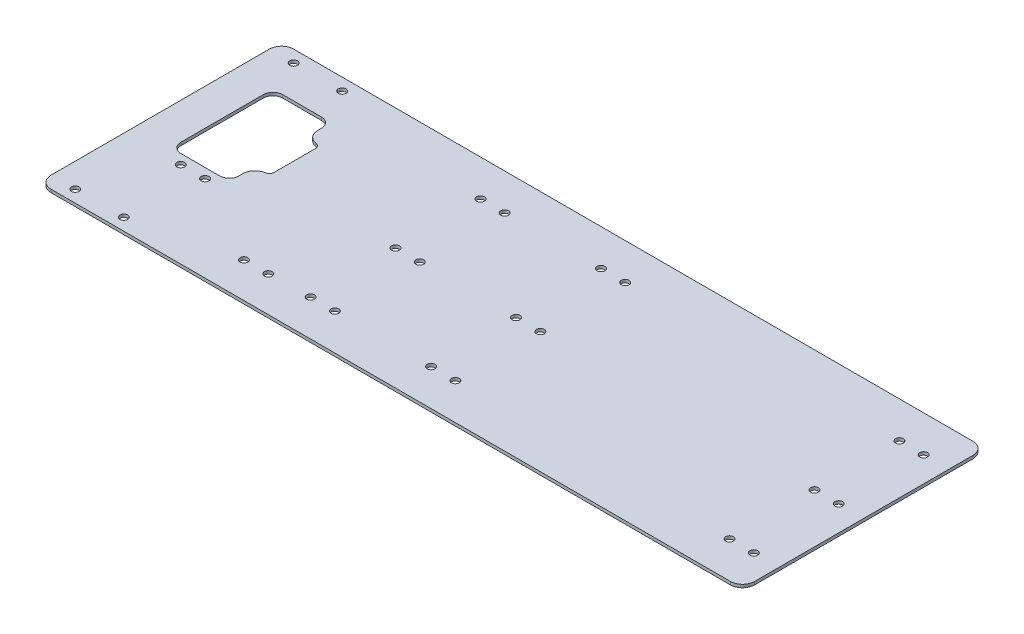
SolidWorks part; units mm, degrees
ref_plane "Front Plane" through (0, 0, 0) normal (0, 0, 1) x (1, 0, 0)
ref_plane "Top Plane" through (0, 0, 0) normal (0, 1, 0) x (1, 0, 0)
ref_plane "Right Plane" through (0, 0, 0) normal (1, 0, 0) x (0, 0, -1)
sketch "Sketch1" plane through (0, 0, 0) normal (0, 1, 0) x (1, 0, 0)
  line L0 (171.0189, 63.5) -> (171.0189, 44.45) construction
  line L1 (184.15, 63.5) -> (-184.15, 63.5)
  line L2 (184.15, 63.5) -> (184.15, -63.5)
  line L3 (184.15, -63.5) -> (-184.15, -63.5)
  line L4 (-184.15, 63.5) -> (-184.15, -63.5)
  line L5 (184.15, 63.5) -> (-184.15, -63.5) construction
  line L6 (184.15, -63.5) -> (-184.15, 63.5) construction
  line L7 (-128.2684, -0.635) -> (-128.2684, 31.115) construction
  line L8 (-128.2684, 31.115) -> (-134.6184, 31.115) construction
  line L9 (-128.2684, 5.715) -> (-134.6184, 5.715) construction
  line L12 (-165.0984, -13.335) -> (-165.0984, 40.005)
  line L15 (-134.6184, -13.335) -> (-165.0984, -13.335)
  line L17 (-134.6184, 40.005) -> (-165.0984, 40.005)
  line L18 (0, 63.5) -> (0, -63.5) construction
  line L19 (-134.6184, 40.005) -> (-134.6184, -13.335)
  line L20 (171.0189, 44.45) -> (184.15, 44.45) construction
  line L21 (0, 0) -> (-126.9984, 0) construction
  line L22 (-82.55, -45.0215) -> (-95.25, -45.0215) construction
  line L23 (171.0189, 44.45) -> (171.0189, 0) construction
  line L25 (171.0189, 0) -> (171.0189, -44.45) construction
  line L26 (171.0189, 44.45) -> (158.3189, 44.45) construction
  line L30 (171.0189, 0) -> (158.3189, 0) construction
  line L31 (171.0189, -44.45) -> (158.3189, -44.45) construction
  line L32 (158.3189, 44.45) -> (14.8089, 44.45) construction
  line L33 (14.8089, 44.45) -> (14.8089, 0) construction
  line L34 (14.8089, 0) -> (14.8089, -44.45) construction
  line L35 (-146.05, -57.15) -> (-184.15, -57.15) construction
  line L36 (-146.05, 57.15) -> (-184.15, 57.15) construction
  line L37 (-128.2684, -0.635) -> (-128.2684, 5.715) construction
  line L38 (-184.15, -18.415) -> (-154.94, -18.415) construction
  line L39 (-154.94, -18.415) -> (-142.24, -18.415) construction
  line L40 (-134.6184, 26.67) -> (-126.9984, 26.67)
  line L41 (-126.9984, 26.67) -> (-126.9984, 0)
  line L42 (-126.9984, 0) -> (-134.6184, 0)
  line L43 (14.8089, 44.45) -> (2.1089, 44.45) construction
  line L44 (14.8089, 0) -> (2.1089, 0) construction
  line L45 (14.8089, -44.45) -> (2.1089, -44.45) construction
  line L46 (2.1089, 44.45) -> (-48.2678, 44.45) construction
  line L47 (-48.2678, 44.45) -> (-60.9678, 44.45) construction
  line L48 (-48.2678, 44.45) -> (-48.2678, 0) construction
  line L49 (-48.2678, 0) -> (-60.9678, 0) construction
  line L50 (-48.2678, 0) -> (-48.2678, -44.45) construction
  line L51 (-48.2678, -44.45) -> (-60.9678, -44.45) construction
  circle A12 centre (-146.05, -57.15) radius 2.032
  circle A13 centre (-171.45, -57.15) radius 2.032
  circle A14 centre (-146.05, 57.15) radius 2.032
  circle A15 centre (-171.45, 57.15) radius 2.032
  circle A18 centre (-154.94, -18.415) radius 2.032
  circle A19 centre (-142.24, -18.415) radius 2.032
  circle A20 centre (-95.25, -45.0215) radius 2.032
  circle A21 centre (-82.55, -45.0215) radius 2.032
  circle A24 centre (171.0189, 44.45) radius 2.032
  circle A25 centre (171.0189, 0) radius 2.032
  circle A26 centre (171.0189, -44.45) radius 2.032
  circle A27 centre (158.3189, 44.45) radius 2.032
  circle A28 centre (158.3189, 0) radius 2.032
  circle A29 centre (158.3189, -44.45) radius 2.032
  circle A30 centre (2.1089, 44.45) radius 2.032
  circle A31 centre (2.1089, 0) radius 2.032
  circle A32 centre (2.1089, -44.45) radius 2.032
  circle A33 centre (14.8089, -44.45) radius 2.032
  circle A34 centre (14.8089, 0) radius 2.032
  circle A35 centre (14.8089, 44.45) radius 2.032
  circle A36 centre (-60.9678, 44.45) radius 2.032
  circle A37 centre (-48.2678, 44.45) radius 2.032
  circle A38 centre (-60.9678, 0) radius 2.032
  circle A39 centre (-60.9678, -44.45) radius 2.032
  circle A40 centre (-48.2678, -44.45) radius 2.032
  circle A41 centre (-48.2678, 0) radius 2.032
  point P0 (0, 0)
  point P11 (-128.2684, -0.635)
  point P13 (-134.6184, 31.115)
  point P17 (-134.6184, 5.715)
  point P37 (0, 0)
  dimension "D5" = 13.335
  dimension "D6" = 29.21
  dimension "D18" = 12.7
  dimension "D13" = 4.064
  dimension "D23" = 44.45
  dimension "D24" = 44.45
  dimension "D31" = 12.7
  dimension "D32" = 143.51
  dimension "D35" = 50.3767
  dimension "D1" = 368.3
  dimension "D2" = 127
  dimension "D3" = 128.27
  dimension "D4" = 25.4
  dimension "D7" = 6.35
  dimension "D8" = 30.48
  dimension "D9" = 53.34
  dimension "D10" = 8.89
  dimension "D11" = 19.05
  dimension "D12" = 12.7
  dimension "D14" = 38.1
  dimension "D15" = 6.35
  dimension "D16" = 12.7
  dimension "D17" = 6.35
  dimension "D19" = 31.75
  dimension "D20" = 19.05
  dimension "D21" = 13.1311
  dimension "D22" = 5.08
  dimension "D25" = 88.9
  dimension "D26" = 12.7
  dimension "D27" = 7.62
  dimension "D28" = 26.67
  dimension "D29" = 13.335
  dimension "D30" = 18.4785
  dimension "D33" = 44.45
  dimension "D34" = 44.45
extrude "Boss-Extrude1" add sketch "Sketch1" along normal blind 1.5875 contours L1 L4 L3 L2 A21 A20 A18 A14 A12 L41 L42 L19 L15 L12 L17 L40 A13 A15 A19 region at (6.1738, 0, 0.5099)
sketch "Sketch2" plane through (0, 1.5875, 0) normal (0, 1, 0) x (1, 0, 0)
  line L0 (-69.85, 63.5) -> (-69.85, -63.5)
  line L1 (184.15, 63.5) -> (-184.15, 63.5) construction
  line L2 (184.15, -63.5) -> (-184.15, -63.5) construction
  circle A0 centre (-82.55, -45.0215) radius 2.032 construction
  dimension "D1" = 12.7
extrude "Cut-Extrude1" [suppressed] cut sketch "Sketch2" against normal through all flip side to cut
fillet "Fillet1" radius 5.08 4 edges at (-134.6184, 0.7937, 13.335) (-165.0984, 0.7937, 13.335) (-165.0984, 0.7937, -40.005) (-134.6184, 0.7937, -40.005)
fillet "Fillet3" radius 6.35 4 edges at (184.15, 0.7937, 63.5) (184.15, 0.7937, -63.5) (-184.15, 0.7937, 63.5) (-184.15, 0.7937, -63.5)
fillet "Fillet4" radius 2.54 2 edges at (-126.9984, 0.7937, 0) (-126.9984, 0.7937, -26.67)
fillet "Fillet5" radius 6.35 2 edges at (-134.6184, 0.7937, 0) (-134.6184, 0.7937, -26.67)
fillet "Fillet6" [suppressed] radius 6.35
sketch "Sketch3" plane through (0, 1.5875, 0) normal (0, 1, 0) x (1, 0, 0)
  circle A0 centre (25.4, -25.4) radius 2.032
  circle A1 centre (25.4, 25.4) radius 2.032
  arc A2 (10.7648, -26.0196) -> (10.7648, -24.7804) centre (12.7, -25.4) ccw construction
  circle A3 centre (25.4, -25.4) radius 2.032 construction
  circle A4 centre (25.4, 25.4) radius 2.032 construction
  arc A5 (10.7648, 24.7804) -> (10.7648, 26.0196) centre (12.7, 25.4) ccw construction
  arc A6 (10.7648, 24.7804) -> (10.7648, 26.0196) centre (12.7, 25.4) ccw
  arc A7 (10.7648, -26.0196) -> (10.7648, -24.7804) centre (12.7, -25.4) ccw
  circle A9 centre (162.56, -44.45) radius 2.032 construction
  circle A10 centre (162.56, 44.45) radius 2.032 construction
  circle A12 centre (-2.54, -25.4) radius 2.032 construction
  circle A15 centre (-73.66, 44.45) radius 2.032 construction
  circle A16 centre (-73.66, -44.45) radius 2.032 construction
  circle A17 centre (25.4, -25.4) radius 2.032
  circle A18 centre (25.4, 25.4) radius 2.032
  circle A19 centre (-15.24, -25.4) radius 2.032 construction
  circle A20 centre (-15.24, 25.4) radius 2.032 construction
  circle A23 centre (162.56, -44.45) radius 2.032
  circle A24 centre (162.56, 44.45) radius 2.032
  circle A29 centre (12.7, -25.4) radius 2.032
  circle A31 centre (12.7, 25.4) radius 2.032
  circle A32 centre (175.26, 44.45) radius 2.032 construction
  circle A33 centre (175.26, -44.45) radius 2.032 construction
  circle A34 centre (175.26, 44.45) radius 2.032
  circle A35 centre (175.26, -44.45) radius 2.032
  circle A36 centre (-2.54, 25.4) radius 2.032 construction
  circle A41 centre (-2.54, -25.4) radius 2.032
  circle A42 centre (-2.54, 25.4) radius 2.032
  circle A54 centre (-73.66, 44.45) radius 2.032
  circle A55 centre (-73.66, -44.45) radius 2.032
  circle A56 centre (-15.24, -25.4) radius 2.032
  circle A57 centre (-15.24, 25.4) radius 2.032
extrude "Cut-Extrude5" [suppressed] cut sketch "Sketch3" against normal through all contours A55 | A54 | A57 | A56 | A41 | A0 | A42 | A31 | A29 | A1
equation "\".80.55in\"=0.55"
